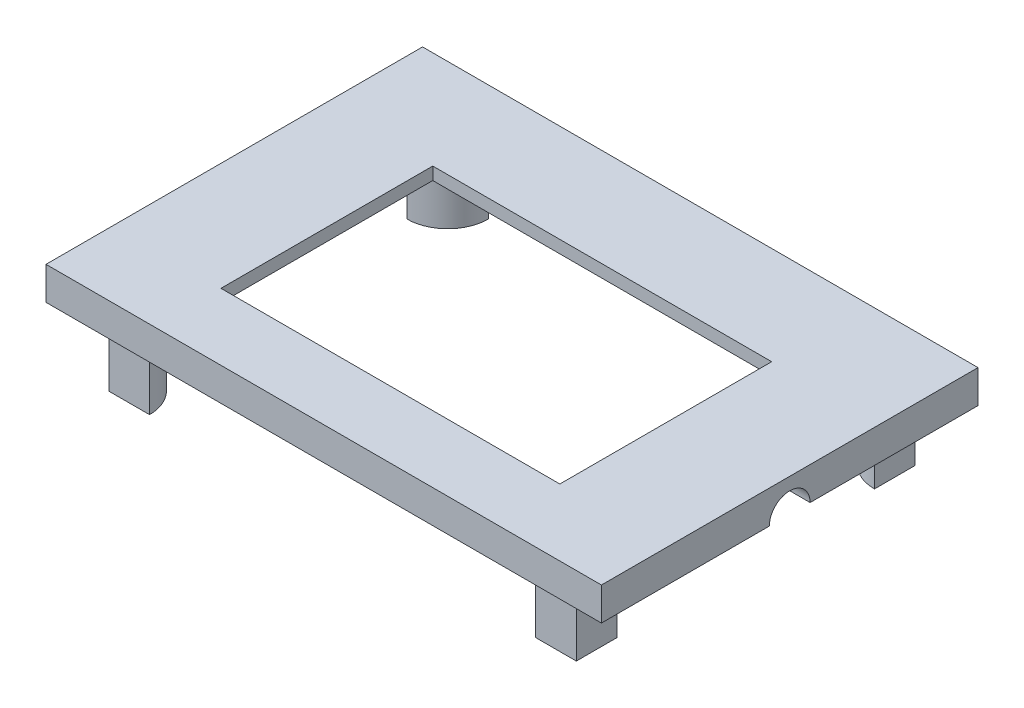
SolidWorks part; units mm, degrees
ref_plane "Alzado" through (0, 0, 0) normal (0, 0, 1) x (1, 0, 0)
ref_plane "Planta" through (0, 0, 0) normal (0, 1, 0) x (1, 0, 0)
ref_plane "Vista lateral" through (0, 0, 0) normal (1, 0, 0) x (0, 0, -1)
sketch "Croquis1" plane through (0, 0, 0) normal (0, 1, 0) x (1, 0, 0)
  line L0 (0, 22) -> (0, -2) construction
  line L1 (-30.2, -22) -> (30.2, -22)
  line L2 (-30.2, -22) -> (-30.2, 22)
  line L3 (-30.2, 22) -> (30.2, 22)
  line L4 (30.2, -22) -> (30.2, 22)
  line L5 (-30.2, -22) -> (30.2, 22) construction
  line L6 (-30.2, 22) -> (30.2, -22) construction
  line L7 (-35.4, -24) -> (35.4, -24)
  line L8 (-35.4, -24) -> (-35.4, 24)
  line L9 (-35.4, 24) -> (35.4, 24)
  line L10 (35.4, -24) -> (35.4, 24)
  line L11 (-35.4, -24) -> (35.4, 24) construction
  line L12 (-35.4, 24) -> (35.4, -24) construction
  line L13 (-21.6, 11.5) -> (21.6, 11.5)
  line L14 (-21.6, 11.5) -> (-21.6, -15.5)
  line L15 (-21.6, -15.5) -> (21.6, -15.5)
  line L16 (21.6, 11.5) -> (21.6, -15.5)
  line L17 (-21.6, 11.5) -> (21.6, -15.5) construction
  line L18 (-21.6, -15.5) -> (21.6, 11.5) construction
  line L19 (-21.6, 17) -> (21.6, 17) construction
  line L20 (-21.6, 17) -> (-21.6, -21) construction
  line L21 (-21.6, -21) -> (21.6, -21) construction
  line L22 (21.6, 17) -> (21.6, -21) construction
  line L23 (-21.6, 17) -> (21.6, -21) construction
  line L24 (-21.6, -21) -> (21.6, 17) construction
  line L26 (-29.8, -21.6) -> (29.8, -21.6)
  line L27 (-29.8, -21.6) -> (-29.8, 21.6)
  line L28 (-29.8, 21.6) -> (29.8, 21.6)
  line L29 (29.8, -21.6) -> (29.8, 21.6)
  line L30 (-29.8, -21.6) -> (29.8, 21.6) construction
  line L31 (-29.8, 21.6) -> (29.8, -21.6) construction
  arc A0 (-29.8, 16.4) -> (-24.6, 21.6) centre (-29.8, 21.6) ccw
  arc A1 (-29.8, -16.4) -> (-24.6, -21.6) centre (-29.8, -21.6) cw
  arc A2 (24.6, -21.6) -> (29.8, -16.4) centre (29.8, -21.6) cw
  arc A3 (24.6, 21.6) -> (29.8, 16.4) centre (29.8, 21.6) ccw
  point P0 (0, 0)
  point P6 (0, 0)
  point P11 (0, -2)
  point P16 (0, -2)
  point P21 (0, -21)
  point P24 (0, -22)
  point P25 (0, 0)
  dimension "D13" = 5.2
  dimension "D1" = 44
  dimension "D2" = 60.4
  dimension "D3" = 5.2
  dimension "D4" = 2
  dimension "D5" = 43.2
  dimension "D6" = 27
  dimension "D7" = 38
  dimension "D8" = 43.2
  dimension "D9" = 5.5
  dimension "D10" = 1
  dimension "D11" = 0.4
  dimension "D12" = 0.4
extrude "Saliente-Extruir1" add sketch "Croquis1" along normal blind 1.6 contours L1 L4 L3 L2 L29 L26 L27 L28 | A1 L27 L26 | L27 A0 L28 | L28 A3 L29 | A2 L26 L29 | A3 L28 A0 L27 A1 L26 A2 L29 L13 L16 L15 L14 | L7 L10 L9 L8 L4 L1 L2 L3 region at (-30.1253, 0, 0) region at (-34.5446, 0, 0) region at (-27.5931, 0, 19.3931) region at (-25.6025, 0, 17.4025) region at (27.5931, 0, 19.3931) region at (-27.5931, 0, -19.3931) region at (27.5931, 0, -19.3931)
extrude "Saliente-Extruir2" add sketch "Croquis1<4>" against normal blind 10.8 contours A1 L27 L26 | L27 A0 L28 | L28 A3 L29 | A2 L26 L29 region at (-27.5931, 0, 19.3931) region at (27.5931, 0, 19.3931) region at (-27.5931, 0, -19.3931) region at (27.5931, 0, -19.3931)
sketch "Croquis1<4>" plane through (0, 0, 0) normal (0, 1, 0) x (1, 0, 0) same geometry as "Croquis1"
extrude "Saliente-Extruir3" add sketch "Croquis1<5>" against normal blind 2.6 contours L1 L4 L3 L2 L29 L26 L27 L28 | L7 L10 L9 L8 L4 L1 L2 L3 region at (-30.1253, 0, 0) region at (-34.5446, 0, 0)
sketch "Croquis1<5>" plane through (0, 0, 0) normal (0, 1, 0) x (1, 0, 0) same geometry as "Croquis1"
ref_plane "Plano1" through (35.4, 0, 0) normal (1, 0, 0) x (0, 0, -1)
sketch "Croquis2" plane through (35.4, 0, 0) normal (1, 0, 0) x (0, 0, -1)
  line L0 (-24, -2.6) -> (24, -2.6) construction
  line L1 (-2.6, -2.6) -> (2.6, -2.6)
  arc A0 (-2.6, -2.6) -> (2.6, -2.6) centre (0, -2.6) cw
  dimension "D1" = 2.6
extrude "Cortar-Extruir1" cut sketch "Croquis2" against normal up to surface (70.8 mm away) up to face at (-35.4, -0.5, 0)
